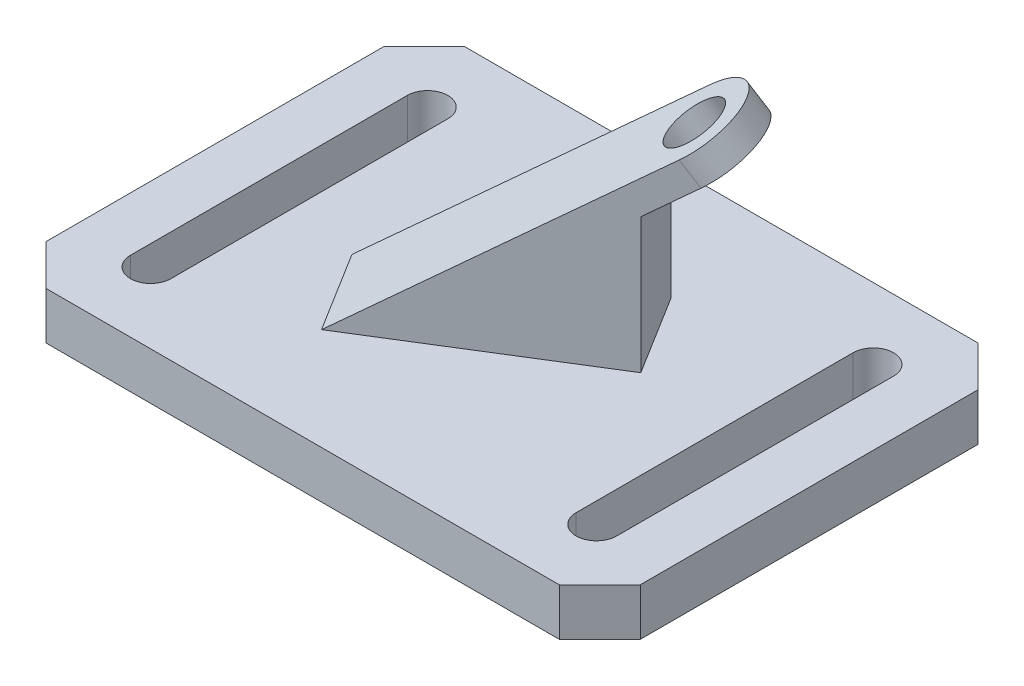
SolidWorks part; units mm, degrees
material "Alloy Steel"
ref_plane "Front Plane" through (0, 0, 0) normal (0, 0, 1) x (1, 0, 0)
ref_plane "Top Plane" through (0, 0, 0) normal (0, 1, 0) x (1, 0, 0)
ref_plane "Right Plane" through (0, 0, 0) normal (1, 0, 0) x (0, 0, -1)
sketch "Sketch1" plane through (0, 0, 0) normal (0, 1, 0) x (1, 0, 0)
  line L0 (-33, -20.5) -> (-33, 20.5) construction
  line L1 (-38, 31) -> (38, 31)
  line L2 (-44, 25) -> (-44, -25)
  line L3 (-38, -31) -> (38, -31)
  line L4 (44, 25) -> (44, -25)
  line L5 (-44, 31) -> (44, -31) construction
  line L6 (-44, -31) -> (44, 31) construction
  line L7 (-36, 20.5) -> (-36, -20.5)
  line L8 (-30, 20.5) -> (-30, -20.5)
  line L9 (-44, 25) -> (-38, 31)
  line L10 (38, 31) -> (44, 25)
  line L11 (38, -31) -> (44, -25)
  line L12 (-44, -25) -> (-38, -31)
  line L13 (-36, 20.5) -> (-36, -20.5)
  line L14 (-30, 20.5) -> (-30, -20.5)
  line L15 (0, 0) -> (0, 31) construction
  line L16 (30, 20.5) -> (30, -20.5)
  line L17 (36, 20.5) -> (36, -20.5)
  arc A0 (-30, 20.5) -> (-36, 20.5) centre (-33, 20.5) ccw
  arc A1 (-36, -20.5) -> (-30, -20.5) centre (-33, -20.5) ccw
  arc A2 (30, 20.5) -> (36, 20.5) centre (33, 20.5) cw
  arc A3 (36, -20.5) -> (30, -20.5) centre (33, -20.5) cw
  point P0 (0, 0)
  point P10 (-33, 0)
  point P29 (0, 0)
  point P30 (0, 0)
  point P31 (10.1221, 21.8062)
  point P32 (0, 31)
  dimension "D4" = 6
  dimension "D1" = 88
  dimension "D2" = 62
  dimension "D3" = 41
  dimension "D5" = 8
extrude "Boss-Extrude1" add sketch "Sketch1" along normal blind 7 contours L2 L12 L3 L11 L4 L10 L1 L9 A1 L7 A0 L8 L17 A3 L16 A2 region at (0, 0, 0)
ref_axis "Axis1" through (-33, 0, 20.5) along (0.8494, 0, -0.5277)
ref_plane "Plane1" through (0, 0, 0) normal (0.5277, 0, 0.8494) x (0.8494, 0, -0.5277)
sketch "Sketch3" plane through (0, 0, 0) normal (0.5277, 0, 0.8494) x (0.8494, 0, -0.5277)
  line L0 (-18.8491, 7) -> (13.5576, 30.5448) construction
  line L1 (-48.6369, 7) -> (15.9206, 7) construction
  line L2 (-12.0439, 7) -> (15.4838, 27)
  line L3 (15.4838, 27) -> (15.4838, 7)
  line L4 (50.5675, 7) -> (24.1833, 7) construction
  line L5 (15.4838, 7) -> (-12.0439, 7)
  line L6 (-36.3007, 7) -> (-41.8491, 7) construction
  point P12 (19.5676, 27)
  point P13 (13.5576, 30.5448)
  dimension "D1" = 20
  dimension "D2" = 20
  dimension "D3" = 36
  dimension "D4" = 4
extrude "Boss-Extrude2" add sketch "Sketch3" along normal mid plane 14
sketch "Sketch4" plane through (-6.3621, 10.3088, 3.9522) normal (-0.4993, 0.809, 0.3102) x (0.8664, 0.4662, 0.1787)
  line L0 (-13.4869, -1.5305) -> (24.6049, 27.7187)
  line L1 (18.2597, 22.8465) -> (-8.728, 2.1237) construction
  line L2 (-13.4869, -1.5305) -> (-4.9605, -12.6345)
  line L3 (-4.9605, -12.6345) -> (33.1313, 16.6146)
  line L4 (26.7861, 11.7424) -> (18.2597, 22.8465) construction
  line L5 (26.7861, 11.7424) -> (18.2597, 22.8465) construction
  line L7 (-0.2016, -8.9804) -> (17.4621, 4.5829) construction
  line L11 (-0.2016, -8.9804) -> (-8.728, 2.1237) construction
  arc A0 (33.1313, 16.6146) -> (24.6049, 27.7187) centre (28.8681, 22.1667) ccw
  circle A1 centre (28.8681, 22.1667) radius 4
  point P2 (-47.8971, 80.9172)
  point P10 (0, -8.9804)
  point P13 (0, -8.9804)
  point P14 (-114.1107, 97.6953)
  point P15 (0, 0)
  point P16 (-115.1921, 101.7266)
  point P17 (0, 0)
  point P20 (0, 0)
  dimension "D2" = 8
  dimension "D1" = 8
  dimension "D3" = 6
extrude "Boss-Extrude3" add sketch "Sketch4" along normal blind 4
